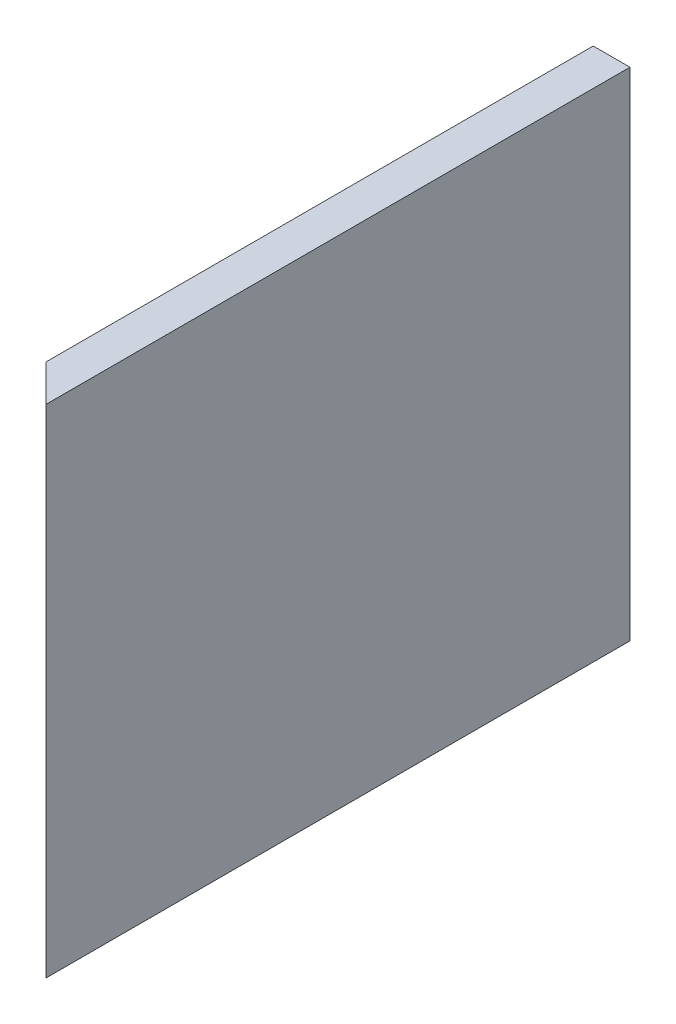
SolidWorks part; units mm, degrees
material "Cedar"
ref_plane "Front Plane" through (0, 0, 0) normal (0, 0, 1) x (1, 0, 0)
ref_plane "Top Plane" through (0, 0, 0) normal (0, 1, 0) x (1, 0, 0)
ref_plane "Right Plane" through (0, 0, 0) normal (1, 0, 0) x (0, 0, -1)
ref_plane "Plane1" through (0, 0, 0) normal (-0.7071, 0, 0.7071) x (0.7071, 0, 0.7071)
sketch "Sketch2" plane through (0, 0, 0) normal (0, 0, 1) x (1, 0, 0)
  line L0 (189.1284, 0) -> (201.8284, 0)
  line L1 (201.8284, 0) -> (201.8284, 171.7294)
  line L2 (201.8284, 171.7294) -> (189.1284, 171.7294)
  line L3 (189.1284, 171.7294) -> (189.1284, 0)
  line L4 (0, 0) -> (189.1284, 0) construction
  line L5 (189.1284, 0) -> (189.1284, 177.6975) construction
  dimension "D1" = 0
  dimension "D2" = 12.7
  dimension "D3" = 171.7294
  dimension "D4" = 201.8284
  dimension "D5" = 171.7294
extrude "Boss-Extrude2" add sketch "Sketch2" along normal up to surface (201.8284 mm away) up to plane "Plane1"
mirror "Mirror1" [suppressed] about plane through (0, 0, 0) normal (-0.7071, 0, 0.7071)
